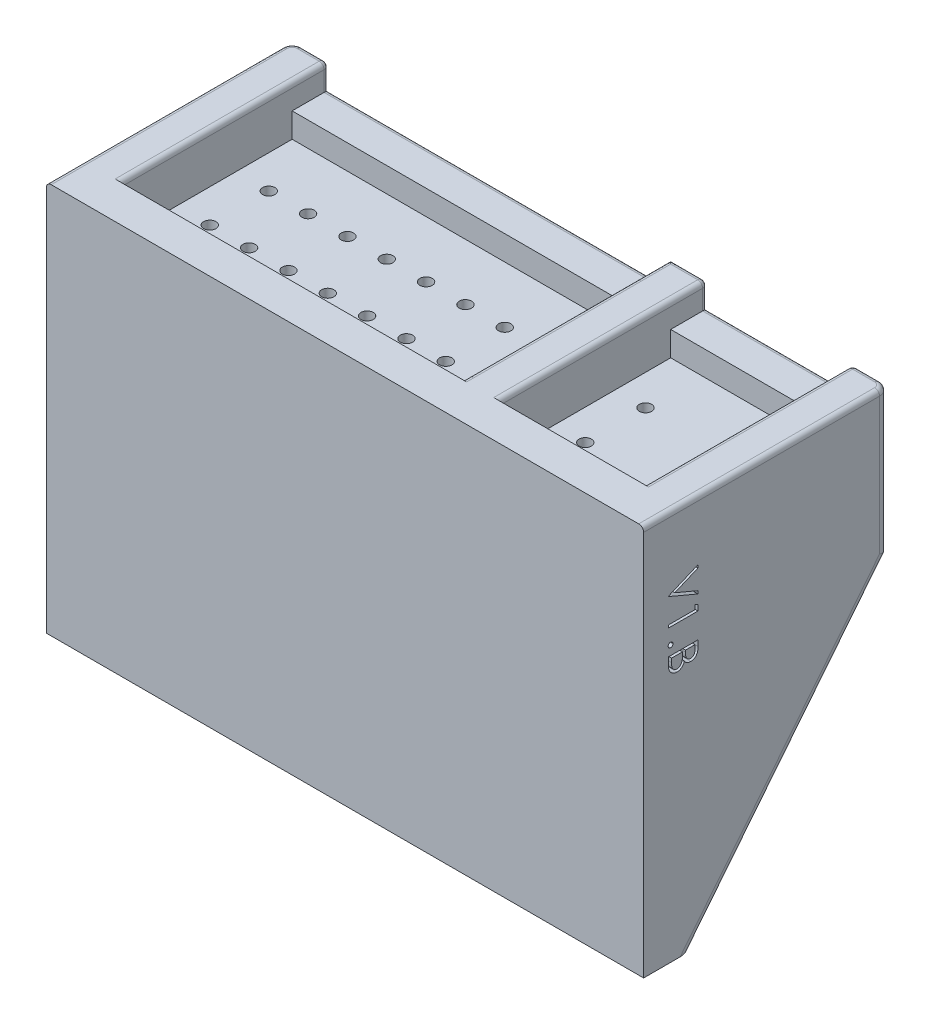
SolidWorks part; units mm, degrees
ref_plane "Front Plane" through (0, 0, 0) normal (0, 0, 1) x (1, 0, 0)
ref_plane "Top Plane" through (0, 0, 0) normal (0, 1, 0) x (1, 0, 0)
ref_plane "Right Plane" through (0, 0, 0) normal (1, 0, 0) x (0, 0, -1)
sketch "Sketch1" plane through (0, 0, 0) normal (0, 1, 0) x (1, 0, 0)
  line L1 (-60.75, -25) -> (60.75, -25)
  line L2 (-60.75, -25) -> (-60.75, 25)
  line L3 (-60.75, 25) -> (60.75, 25)
  line L4 (60.75, -25) -> (60.75, 25)
  line L5 (-60.75, -25) -> (60.75, 25) construction
  line L6 (-60.75, 25) -> (60.75, -25) construction
  point P0 (0, 0)
  dimension "D1" = 121.5
  dimension "D2" = 50
extrude "Boss-Extrude1" add sketch "Sketch1" along normal blind 29.5
sketch "Sketch2" plane through (0, 29.5, 0) normal (0, 1, 0) x (1, 0, 0)
  line L1 (23.75, -17.5) -> (53.25, -17.5)
  line L2 (23.75, -17.5) -> (23.75, 17.5)
  line L3 (23.75, 17.5) -> (53.25, 17.5)
  line L4 (53.25, -17.5) -> (53.25, 17.5)
  line L5 (23.75, -17.5) -> (53.25, 17.5) construction
  line L6 (23.75, 17.5) -> (53.25, -17.5) construction
  line L7 (60.75, -25) -> (60.75, 25) construction
  point P0 (38.5, 0)
  dimension "D1" = 35
  dimension "D2" = 29.5
  dimension "D3" = 7.5
extrude "Cut-Extrude1" cut sketch "Sketch2" against normal blind 10
sketch "Sketch3" plane through (0, 29.5, 0) normal (0, 1, 0) x (1, 0, 0)
  line L0 (23.75, 17.5) -> (23.75, -17.5) construction
  line L1 (-53.25, -17.5) -> (16.25, -17.5)
  line L2 (-53.25, -17.5) -> (-53.25, 17.5)
  line L3 (-53.25, 17.5) -> (16.25, 17.5)
  line L4 (16.25, -17.5) -> (16.25, 17.5)
  line L5 (-53.25, -17.5) -> (16.25, 17.5) construction
  line L6 (-53.25, 17.5) -> (16.25, -17.5) construction
  point P0 (-18.5, 0)
  dimension "D1" = 7.5
  dimension "D2" = 69.5
  dimension "D3" = 35
extrude "Cut-Extrude2" cut sketch "Sketch3" against normal blind 10
sketch "Sketch5" plane through (0, 19.5, 0) normal (0, 1, 0) x (1, 0, 0)
  line L0 (-48.7346, 0) -> (32.4983, 0) construction
  line L2 (-46.5, 6) -> (-38.5, 6) construction
  line L4 (-53.25, 17.5) -> (16.25, -17.5) construction
  line L5 (16.25, 17.5) -> (-53.25, -17.5) construction
  line L6 (-18.5, 0) -> (-41.795, 0) construction
  line L7 (-18.5, 0) -> (-18.5, 11.1048) construction
  circle A19 centre (-46.5, 6) radius 1.25
  circle A20 centre (-38.5, 6) radius 1.25
  circle A21 centre (-30.5, 6) radius 1.25
  circle A22 centre (-22.5, 6) radius 1.25
  circle A23 centre (-14.5, 6) radius 1.25
  circle A24 centre (-6.5, 6) radius 1.25
  circle A25 centre (1.5, 6) radius 1.25
  circle A26 centre (9.5, 6) radius 1.25
  circle A27 centre (-38.5, -6) radius 1.25
  circle A28 centre (-30.5, -6) radius 1.25
  circle A29 centre (-22.5, -6) radius 1.25
  circle A30 centre (-14.5, -6) radius 1.25
  circle A31 centre (-6.5, -6) radius 1.25
  circle A32 centre (1.5, -6) radius 1.25
  circle A33 centre (9.5, -6) radius 1.25
  circle A34 centre (-46.5, -6) radius 1.25
  dimension "D6" = 8
  dimension "D7" = 2.5
  dimension "D4" = 28
  dimension "D1" = 6
  dimension "D2" = 0
  dimension "D3" = 2
extrude "Cut-Extrude4" cut sketch "Sketch5" against normal through all
sketch "Sketch6" plane through (0, 19.5, 0) normal (0, 1, 0) x (1, 0, 0)
  line L0 (30, 6.125) -> (46, 6.125) construction
  line L1 (46, 6.125) -> (46, -5.875) construction
  line L2 (46, -5.875) -> (30, -5.875) construction
  line L3 (30, -5.875) -> (30, 6.125) construction
  line L6 (23.75, 17.5) -> (53.25, -17.25) construction
  line L7 (53.25, -17.5) -> (53.25, 17.5) construction
  line L8 (53.25, -17.5) -> (53.25, 17.5) construction
  line L9 (53.25, 17.5) -> (23.75, -17.5) construction
  circle A0 centre (30, 6.125) radius 1.25
  circle A1 centre (46, 6.125) radius 1.25
  point P17 (38.5, 0.125)
  dimension "D5" = 2.5
  dimension "D6" = 2.5
  dimension "D1" = 6
  dimension "D3" = 16
  dimension "D4" = 12
extrude "Cut-Extrude5" cut sketch "Sketch6" against normal through all
mirror "Mirror3" about plane through (0, 0, 0) normal (0, 0, 1) of "Cut-Extrude5"
sketch "Sketch8" plane through (0, 29.5, 0) normal (0, 1, 0) x (1, 0, 0)
  line L0 (-53.25, 17.5) -> (16.25, 17.5)
  line L1 (16.25, 17.5) -> (16.25, 25)
  line L2 (60.75, 25) -> (-60.75, 25) construction
  line L3 (16.25, 25) -> (-53.25, 25)
  line L4 (-53.25, 25) -> (-53.25, 17.5)
  line L5 (23.75, 17.5) -> (53.25, 17.5)
  line L6 (53.25, 17.5) -> (53.25, 25)
  line L7 (53.25, 25) -> (23.75, 25)
  line L8 (23.75, 25) -> (23.75, 17.5)
extrude "Cut-Extrude7" cut sketch "Sketch8" against normal blind 5
fillet "Fillet1" radius 1 14 edges at (53.25, 27, -25) (-18.5, 24.5, -25) (38.5, 24.5, -25) (-53.25, 27, -25) (23.75, 27, -25) (16.25, 29.5, -3.75) (20, 29.5, -25) (23.75, 29.5, -3.75) (53.25, 29.5, -3.75) (57, 29.5, -25) (60.75, 29.5, 0) (-60.75, 29.5, 0) (-57, 29.5, -25) (-53.25, 29.5, -3.75)
sketch "Sketch9" plane through (0, 0, 0) normal (0, -1, 0) x (1, 0, 0)
  line L0 (-60.75, -25) -> (-60.75, 25) construction
  line L1 (60.75, 25) -> (-60.75, 25)
  line L2 (60.75, 25) -> (60.75, 15)
  line L3 (60.75, 15) -> (-60.75, 15)
  line L4 (-60.75, 25) -> (-60.75, 15)
  dimension "D1" = 10
extrude "Boss-Extrude2" add sketch "Sketch9" along normal blind 50
sketch "Sketch10" plane through (-60.75, 0, 0) normal (-1, 0, 0) x (0, 0, 1)
  line L0 (-25, 0) -> (15, -50)
  line L1 (15, -50) -> (15, 0)
  line L2 (15, 0) -> (-25, 0)
extrude "Boss-Extrude3" add sketch "Sketch10" against normal blind 10
mirror "Mirror4" about plane through (0, 0, 0) normal (1, 0, 0) of "Boss-Extrude3"
fillet "Fillet3" radius 2 8 edges at (-60.4571, 29.2071, -24.7071) (60.4571, 29.2071, -24.7071) (60.75, 14.25, -25) (-60.75, 14.25, -25) (-60.75, -25, -5) (60.75, -25, -5) (-50.75, -25, -5) (50.75, -25, -5)
sketch "Sketch11" plane through (0, 0, 0) normal (0, -1, 0) x (1, 0, 0)
  line L0 (50.75, 15) -> (50.75, -22.4388) construction
  line L1 (50.75, -12.125) -> (-50.75, -12.125)
  line L2 (50.75, -12.125) -> (50.75, 12.125)
  line L3 (50.75, 12.125) -> (-50.75, 12.125)
  line L4 (-50.75, -12.125) -> (-50.75, 12.125)
  line L5 (-50.75, 15) -> (-50.75, -22.4388) construction
  circle A0 centre (46, -6.125) radius 1.25 construction
  circle A1 centre (46, 6.125) radius 1.25 construction
  dimension "D1" = 6
  dimension "D2" = 6
extrude "Recess" cut sketch "Sketch11" against normal blind 2
sketch "Sketch12" plane through (60.75, 0, 0) normal (1, 0, 0) x (0, 0, -1)
  line L0 (-19.9408, 17.5839) -> (-19.9408, -4.1264) construction
  text T0 "V1.B" font "Century Gothic" height 6
extrude "Cut-Extrude9" cut sketch "Sketch12" against normal blind 2
